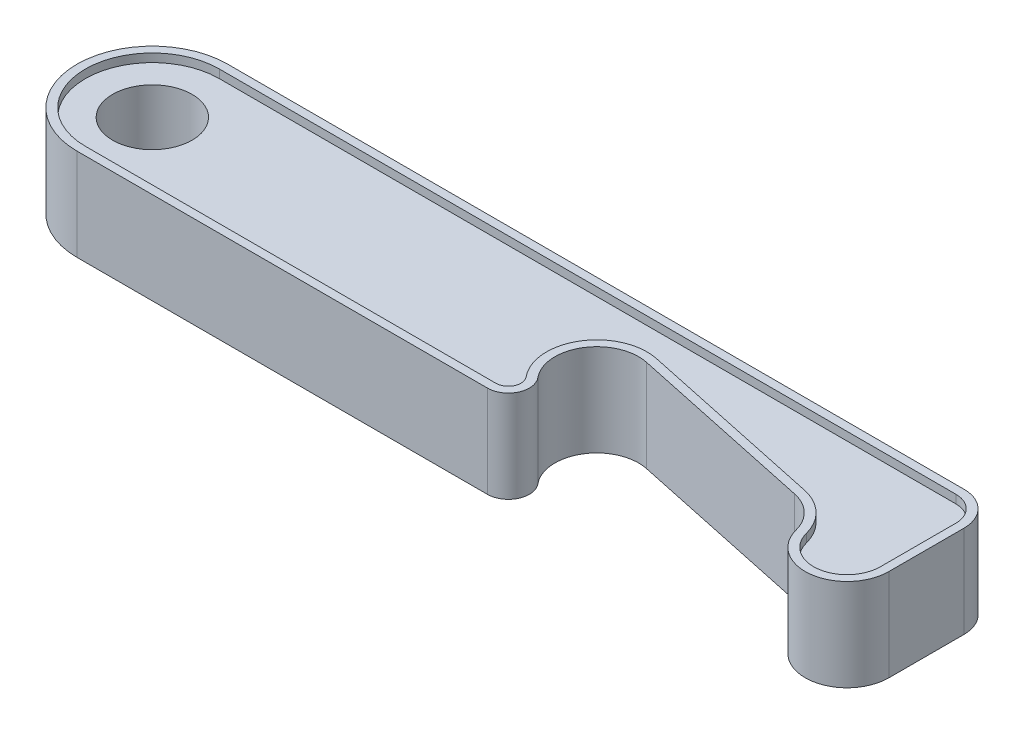
SolidWorks part; units mm, degrees
ref_plane "Front Plane" through (0, 0, 0) normal (0, 0, 1) x (1, 0, 0)
ref_plane "Top Plane" through (0, 0, 0) normal (0, 1, 0) x (1, 0, 0)
ref_plane "Right Plane" through (0, 0, 0) normal (1, 0, 0) x (0, 0, -1)
sketch "Sketch1" plane through (0, 0, 0) normal (0, 1, 0) x (1, 0, 0)
  line L0 (0, 9) -> (88, 9)
  line L1 (0, -9) -> (49.0402, -9)
  line L2 (92, 5) -> (92, -4)
  line L3 (0, 8) -> (88, 8)
  line L4 (91, 5) -> (91, -4)
  line L5 (55.8571, 3.1733) -> (78.3571, -1.6093)
  line L6 (49.0402, -9) -> (72.0312, -9) construction
  line L7 (49.0402, -9) -> (89.6935, -9) construction
  line L8 (56.065, 4.1514) -> (78.565, -0.6311)
  line L9 (0, -8) -> (49.0402, -8)
  circle A0 centre (0, 0) radius 4.75
  arc A1 (0, 9) -> (0, -9) centre (0, 0) ccw
  arc A2 (92, 5) -> (88, 9) centre (88, 5) ccw
  arc A3 (82.1588, -5.25) -> (92, -4) centre (87, -4) ccw
  arc A4 (49.0402, -9) -> (50.966, -4.9058) centre (49.0402, -6.5) ccw
  arc A5 (55.8571, 3.1733) -> (50.966, -4.9058) centre (54.8175, -1.7175) ccw
  arc A6 (82.1588, -5.25) -> (78.3571, -1.6093) centre (77.3175, -6.5) ccw
  arc A7 (91, 5) -> (88, 8) centre (88, 5) ccw
  arc A8 (83.127, -5) -> (91, -4) centre (87, -4) ccw
  arc A9 (83.127, -5) -> (78.565, -0.6311) centre (77.3175, -6.5) ccw
  arc A10 (56.065, 4.1514) -> (50.1957, -5.5435) centre (54.8175, -1.7175) ccw
  arc A11 (49.0402, -8) -> (50.1957, -5.5435) centre (49.0402, -6.5) ccw
  arc A12 (0, 8) -> (0, -8) centre (0, 0) ccw
  point P36 (-9, 0)
  dimension "D1" = 9.5
  dimension "D2" = 4
  dimension "D3" = 12
  dimension "D4" = 5
  dimension "D5" = 5
  dimension "D6" = 22.5
  dimension "D7" = 18
  dimension "D8" = 2.5
  dimension "D9" = 5
  dimension "D10" = 1
  dimension "D11" = 101
extrude "Boss-Extrude1" add sketch "Sketch1" along normal blind 4.5 and the other way blind 4.5 contours L3 A12 L9 A11 A10 L8 A9 A8 L4 A7 A0 region at (38.4301, 0, -0.8544)
extrude "Boss-Extrude2" add sketch "Sketch1<3>" along normal blind 5.5 and the other way blind 5.5 contours A6 A3 L2 A2 L0 A1 L1 A4 A5 L5 A12 L3 A7 L4 A8 A9 L8 A10 A11 L9 region at (44, 0, -8.8974)
sketch "Sketch1<3>" plane through (0, 0, 0) normal (0, 1, 0) x (1, 0, 0) same geometry as "Sketch1"
sketch "Sketch2" plane through (92, 0, 0) normal (1, 0, 0) x (0, 0, -1)
